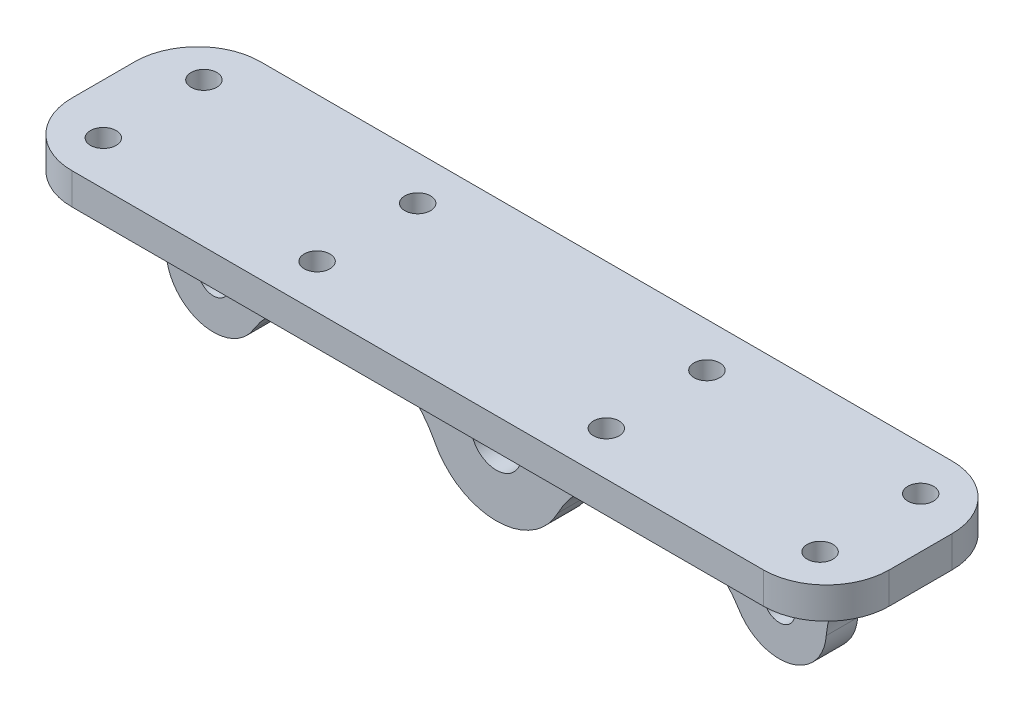
SolidWorks part; units mm, degrees
ref_plane "Front Plane" through (0, 0, 0) normal (0, 0, 1) x (1, 0, 0)
ref_plane "Top Plane" through (0, 0, 0) normal (0, 1, 0) x (1, 0, 0)
ref_plane "Right Plane" through (0, 0, 0) normal (1, 0, 0) x (0, 0, -1)
sketch "Sketch1" plane through (0, 0, 0) normal (0, 0, 1) x (1, 0, 0)
  line L0 (0, -17.6791) -> (0, 20.5964) construction
  line L1 (0, 11) -> (0, -11)
  line L2 (-52.5, 11) -> (-52.5, 0)
  line L3 (0, 11) -> (-52.5, 11)
  circle A0 centre (0, 0) radius 4
  circle A1 centre (-45, 0) radius 2.5
  circle A2 centre (0, 0) radius 74.2 construction
  circle A3 centre (-45, 0) radius 7.5
  circle A4 centre (0, 0) radius 11
  arc A5 (-38.6142, -3.9333) -> (-9.7793, -5.0364) centre (-24.508, -12.6219) cw
  dimension "D1" = 8
  dimension "D2" = 5
  dimension "D4" = 148.4
  dimension "D5" = 22
  dimension "D6" = 15
  dimension "D3" = 45
extrude "Boss-Extrude1" add sketch "Sketch1" against normal mid plane 5 contours A3 A5 A4 L3 | A3 A1 | A3 L3 L2 | L1 A4 A0 region at (-27.5897, 6.8383, 0) region at (-5.1213, 0, 0) region at (-45, 7.2879, 0)
mirror "Mirror1" about plane through (0, 0, -2.5) normal (-1, 0, 0) of "Boss-Extrude1"
sketch "Sketch4" plane through (0, 11, 0) normal (0, 1, 0) x (1, 0, 0)
  line L0 (-52.5, 2.5) -> (-52.5, -2.5) construction
  line L1 (-65, -15) -> (65, -15)
  line L2 (-65, -15) -> (-65, 15)
  line L3 (-65, 15) -> (65, 15)
  line L4 (65, -15) -> (65, 15)
  line L6 (52.5, -2.5) -> (-52.5, -2.5) construction
  line L7 (52.5, 2.5) -> (-52.5, 2.5) construction
  dimension "D1" = 130
  dimension "D2" = 12.5
  dimension "D3" = 12.5
  dimension "D4" = 12.5
extrude "Boss-Extrude2" add sketch "Sketch4" along normal blind 5
fillet "Fillet1" radius 10 4 edges at (-65, 13.5, 15) (-65, 13.5, -15) (65, 13.5, -15) (65, 13.5, 15)
fillet "Fillet2" radius 12.5 2 edges at (-52.5, 11, 0) (52.5, 11, 0)
sketch "Sketch5" plane through (0, 16, 0) normal (0, 1, 0) x (1, 0, 0)
  line L1 (-55, -15) -> (55, -15) construction
  line L2 (55, 15) -> (-55, 15) construction
  line L3 (-65, 5) -> (-65, -5) construction
  circle A0 centre (-57, -8) radius 2.05
  circle A1 centre (-57, 8) radius 2.05
  circle A6 centre (-23, -8) radius 2.05
  circle A7 centre (-23, 8) radius 2.05
  dimension "D2" = 34
  dimension "D3" = 4.1
  dimension "D4" = 4.1
  dimension "D6" = 4.1
  dimension "D11" = 4.1
  dimension "D7" = 7
  dimension "D8" = 8
  dimension "D9" = 8
  dimension "D10" = 7
extrude "Cut-Extrude1" cut sketch "Sketch5" against normal blind 10
mirror "Mirror2" about plane through (0, 0, 0) normal (1, 0, 0) of "Cut-Extrude1"
ref_plane "Plane1" through (36.5, 0, 0) normal (1, 0, 0) x (0, 0, -1)
sketch "Sketch7" plane through (36.5, 0, 0) normal (1, 0, 0) x (0, 0, -1)
  line L0 (-5, 11) -> (5, 11) construction
  line L1 (5, 16) -> (-5, 16) construction
  line L2 (-5, 16) -> (-5, 11) construction
  line L3 (15, 16) -> (5, 16) construction
  line L4 (5, 11) -> (15, 11) construction
  line L5 (15, 11) -> (15, 16) construction
  line L6 (2.5, -0.5625) -> (2.5, 11) construction
  line L7 (2.5, 11) -> (-2.5, 11) construction
  line L8 (-2.5, 11) -> (-2.5, -0.5625) construction
  line L9 (-2.5, -0.5625) -> (2.5, -0.5625) construction
  line L10 (-5, 11) -> (5, 11)
  line L11 (5, 16) -> (-5, 16)
  line L12 (-5, 16) -> (-5, 11)
  line L13 (15, 16) -> (5, 16)
  line L14 (5, 11) -> (15, 11)
  line L15 (15, 11) -> (15, 16)
  line L16 (2.5, -0.5625) -> (2.5, 11)
  line L17 (2.5, 11) -> (-2.5, 11)
  line L18 (-2.5, 11) -> (-2.5, -0.5625)
  line L19 (-2.5, -0.5625) -> (2.5, -0.5625)
  line L20 (2.5, 6) -> (7.5, 11)
  line L21 (2.5, 11) -> (7.5, 11)
  line L22 (2.5, 11) -> (2.5, 6)
  dimension "D1" = 5
  dimension "D2" = 5
extrude "Boss-Extrude3" add sketch "Sketch7" along normal mid plane 5 contours L16 L20 L14 L10 region at (36.5, 9.3333, -4.1667)
pattern_linear "LPattern1" count 2 spacing 23 along (-1, 0, 0) of "Boss-Extrude3"
mirror "Mirror4" about plane through (0, 0, 0) normal (0, 0, 1) of "LPattern1" second plane through (0, 0, 0) second plane normal (1, 0, 0)
